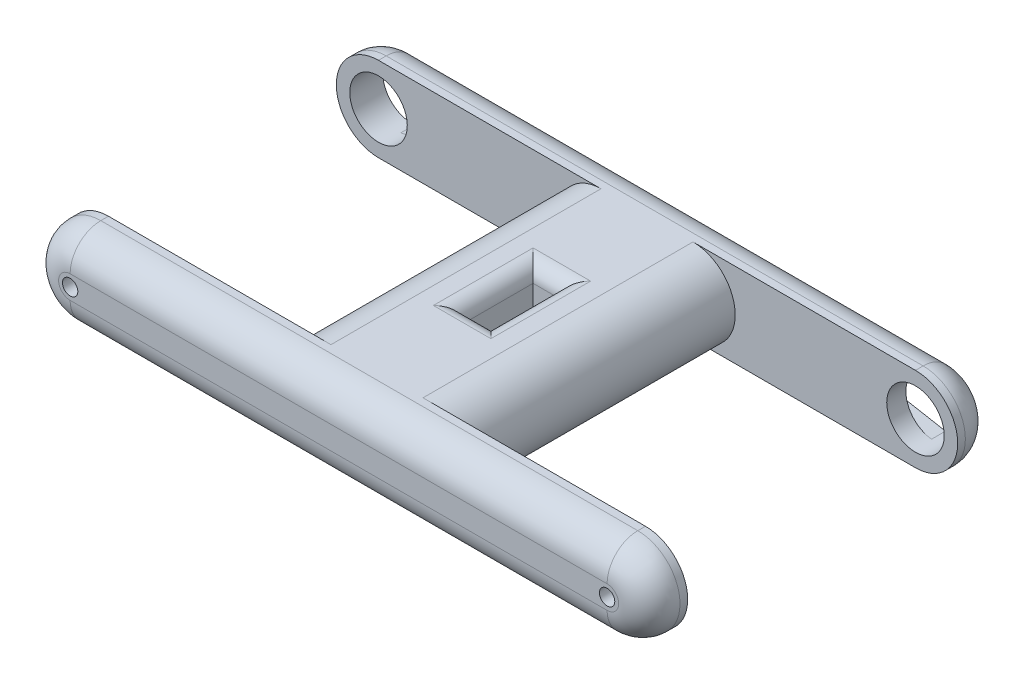
SolidWorks part; units mm, degrees
ref_plane "Plan de face" through (0, 0, 0) normal (0, 0, 1) x (1, 0, 0)
ref_plane "Plan de dessus" through (0, 0, 0) normal (0, 1, 0) x (1, 0, 0)
ref_plane "Plan de droite" through (0, 0, 0) normal (1, 0, 0) x (0, 0, -1)
sketch "Esquisse1" plane through (0, 0, 2042.8959) normal (0, 0, -1) x (-1, 0, 0)
  line L0 (0, 0) -> (-70, 0) construction
  line L1 (0, -5.5) -> (-70, -5.5)
  line L2 (0, 5.5) -> (-70, 5.5)
  arc A0 (0, -5.5) -> (0, 5.5) centre (0, 0) ccw
  arc A1 (-70, 5.5) -> (-70, -5.5) centre (-70, 0) ccw
  circle A2 centre (0, 0) radius 3.75
  circle A3 centre (-70, 0) radius 3.75
  point P3 (-35, 0)
  dimension "D1" = 5.5
  dimension "D3" = 7.5
  dimension "D2" = 70
extrude "Boss.-Extru.1" add sketch "Esquisse1" against normal blind 4 and the other way blind 1
sketch "Esquisse2" plane through (0, 0, 2041.8959) normal (0, 0, -1) x (-1, 0, 0)
  line L0 (-0.4102, -3.7275) -> (-16.2187, -1.988)
  line L1 (-16.2187, 1.988) -> (-0.4102, 3.7275)
  line L2 (-0.4102, 3.7275) -> (-0.4102, -3.7275)
  line L3 (0, 0) -> (-16, 0) construction
  line L4 (-35, 5.5) -> (-35, -5.5) construction
  line L5 (0, 5.5) -> (-70, 5.5) construction
  line L6 (-70, -5.5) -> (0, -5.5) construction
  line L7 (-53.7812, 1.988) -> (-69.5898, 3.7275)
  line L8 (-69.5898, -3.7275) -> (-53.7812, -1.988)
  line L9 (-69.5898, 3.7275) -> (-69.5898, -3.7275)
  arc A1 (-16.2187, 1.988) -> (-16.2187, -1.988) centre (-16, 0) ccw
  circle A2 centre (0, 0) radius 3.75 construction
  arc A3 (-53.7812, 1.988) -> (-53.7812, -1.988) centre (-54, 0) cw
  dimension "D1" = 2
  dimension "D2" = 16
extrude "Enlèv. mat.-Extru.1" cut sketch "Esquisse2" against normal blind 2.5
sketch "Esquisse3" plane through (0, 0, 2046.8959) normal (0, 0, 1) x (1, 0, 0)
  line L0 (29, 0) -> (41, 0) construction
  line L1 (29, 5.5) -> (41, 5.5)
  line L2 (29, -5.5) -> (41, -5.5)
  line L3 (0, 5.5) -> (70, 5.5) construction
  line L4 (70, -5.5) -> (0, -5.5) construction
  line L5 (35, 5.5) -> (35, -5.5) construction
  arc A0 (29, 5.5) -> (29, -5.5) centre (29, 0) ccw
  arc A1 (41, -5.5) -> (41, 5.5) centre (41, 0) ccw
  point P2 (35, 0)
  point P11 (0, 0)
  dimension "D1" = 12
extrude "Boss.-Extru.2" add sketch "Esquisse3" along normal blind 35.2
sketch "Esquisse4" plane through (0, 0, 2082.0959) normal (0, 0, 1) x (1, 0, 0)
  line L0 (0, 0) -> (70, 0) construction
  line L1 (0, 5.5) -> (70, 5.5)
  line L2 (0, -5.5) -> (70, -5.5)
  line L3 (41, 5.5) -> (29, 5.5) construction
  line L4 (35, 5.5) -> (35, -5.5) construction
  line L5 (29, -5.5) -> (41, -5.5) construction
  arc A0 (0, 5.5) -> (0, -5.5) centre (0, 0) ccw
  arc A1 (70, -5.5) -> (70, 5.5) centre (70, 0) ccw
  point P2 (35, 0)
extrude "Boss.-Extru.3" add sketch "Esquisse4" along normal blind 5
sketch "Esquisse5" plane through (0, 0, 2087.0959) normal (0, 0, 1) x (1, 0, 0)
  circle A0 centre (0, 0) radius 1
  circle A1 centre (70, 0) radius 1
  dimension "D1" = 2
extrude "Enlèv. mat.-Extru.2" cut sketch "Esquisse5" against normal blind 5
fillet "Congé1" radius 4 6 edges at (35, 5.5, 2041.8959) (35, -5.5, 2041.8959) (75.5, 0, 2087.0959) (35, -5.5, 2087.0959) (-5.5, 0, 2087.0959) (35, 5.5, 2087.0959)
sketch "Esquisse6" plane through (0, 5.5, 0) normal (0, 1, 0) x (1, 0, 0)
  line L0 (29, -2064.4959) -> (41, -2064.4959) construction
  line L1 (33.25, -2059.9959) -> (36.75, -2059.9959)
  line L2 (33.25, -2059.9959) -> (33.25, -2068.9959)
  line L3 (33.25, -2068.9959) -> (36.75, -2068.9959)
  line L4 (36.75, -2059.9959) -> (36.75, -2068.9959)
  line L5 (33.25, -2059.9959) -> (36.75, -2068.9959) construction
  line L6 (33.25, -2068.9959) -> (36.75, -2059.9959) construction
  line L7 (29, -2082.0959) -> (29, -2046.8959) construction
  line L8 (41, -2082.0959) -> (41, -2046.8959) construction
  point P0 (35, -2064.4959)
  point P11 (35, -2064.4959)
  dimension "D1" = 9
  dimension "D2" = 3.5
extrude "Enlèv. mat.-Extru.3" cut sketch "Esquisse6" against normal through all
fillet "Congé2" radius 2 8 edges at (35, -5.5, 2059.9959) (36.75, -5.5, 2064.4959) (35, -5.5, 2068.9959) (33.25, -5.5, 2064.4959) (35, 5.5, 2068.9959) (35, 5.5, 2059.9959) (36.75, 5.5, 2064.4959) (33.25, 5.5, 2064.4959)
